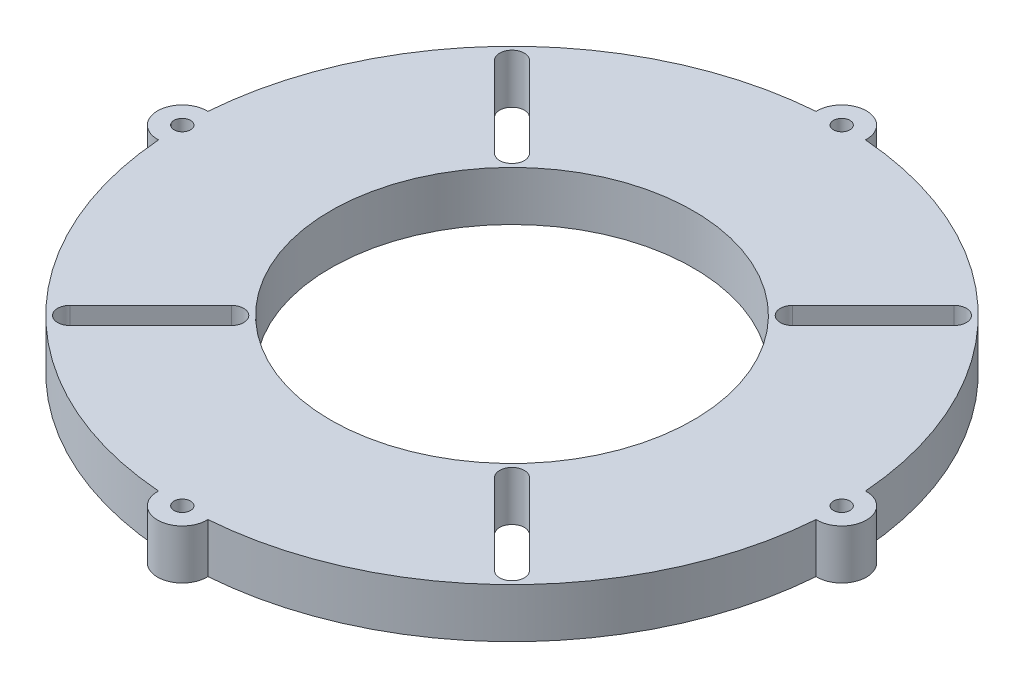
SolidWorks part; units mm, degrees
material "Aluminum 7075-T6 (2)"
ref_plane "Front Plane" through (0, 0, 0) normal (0, 0, 1) x (1, 0, 0)
ref_plane "Top Plane" through (0, 0, 0) normal (0, 1, 0) x (1, 0, 0)
ref_plane "Right Plane" through (0, 0, 0) normal (1, 0, 0) x (0, 0, -1)
sketch "Sketch1" plane through (0, 0, 0) normal (0, 1, 0) x (1, 0, 0)
  circle A0 centre (0, 0) radius 22
  circle A1 centre (0, 0) radius 40
extrude "Boss-Extrude1" add sketch "Sketch1" along normal blind 6 contours A1 | A0
sketch "Sketch2" plane through (0, 6, 0) normal (0, 1, 0) x (1, 0, 0)
  circle A0 centre (40, 0) radius 3
  circle A1 centre (40, 0) radius 1
extrude "Cut-Extrude2" cut sketch "Sketch2" against normal through all contours A1
extrude "Boss-Extrude3" add sketch "Sketch2<6>" against normal blind 6
sketch "Sketch2<6>" plane through (0, 6, 0) normal (0, 1, 0) x (1, 0, 0) same geometry as "Sketch2"
pattern_circular "CirPattern1" count 4 over 360 about axis through (0, 6, 0) along (0, 1, 0) of "Cut-Extrude2", "Boss-Extrude3"
sketch "Sketch4" plane through (0, 6, 0) normal (0, 1, 0) x (1, 0, 0)
  line L0 (-26.8143, -26.8143) -> (-17.0263, -17.0263) construction
  line L1 (-27.8749, -25.7536) -> (-18.087, -15.9657)
  line L2 (-25.7536, -27.8749) -> (-15.9657, -18.087)
  line L3 (-21.9203, -21.9203) -> (0, 0) construction
  arc A0 (-27.8749, -25.7536) -> (-25.7536, -27.8749) centre (-26.8143, -26.8143) ccw
  arc A1 (-15.9657, -18.087) -> (-18.087, -15.9657) centre (-17.0263, -17.0263) ccw
  point P2 (-21.9203, -21.9203)
extrude "Cut-Extrude4" cut sketch "Sketch4" against normal through all
pattern_circular "CirPattern3" count 4 over 360 about axis through (0, 6, 0) along (0, 1, 0) of "Cut-Extrude4"
